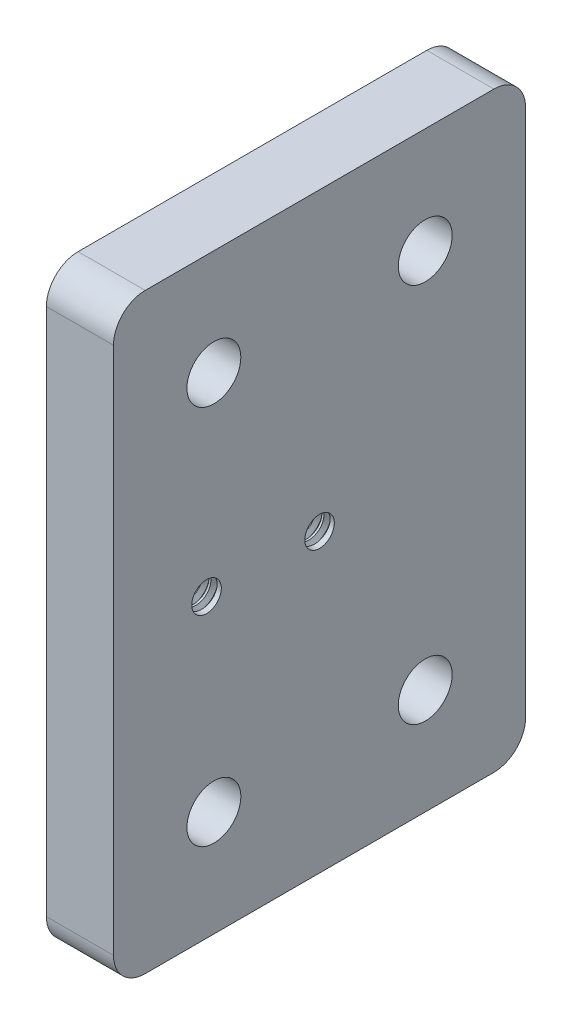
SolidWorks part; units mm, degrees
ref_plane "Front Plane" through (0, 0, 0) normal (0, 0, 1) x (1, 0, 0)
ref_plane "Top Plane" through (0, 0, 0) normal (0, 1, 0) x (1, 0, 0)
ref_plane "Right Plane" through (0, 0, 0) normal (1, 0, 0) x (0, 0, -1)
sketch "Sketch1" plane through (0, 0, 0) normal (1, 0, 0) x (0, 0, -1)
  line L0 (0, 55) -> (0, -55) construction
  line L1 (-10, -18) -> (10, -18) construction
  line L2 (-10, -18) -> (-10, 18) construction
  line L3 (-10, 18) -> (10, 18) construction
  line L4 (10, -18) -> (10, 18) construction
  line L5 (-10, -18) -> (10, 18) construction
  line L6 (-10, 18) -> (10, -18) construction
  line L7 (55, 0) -> (-55, 0) construction
  line L8 (-10.6934, 0) -> (0, 0) construction
  line L10 (-19.5, 28) -> (19.5, 28)
  line L11 (-19.5, 28) -> (-19.5, -28)
  line L12 (-19.5, -28) -> (19.5, -28)
  line L13 (19.5, 28) -> (19.5, -28)
  circle A0 centre (-10, 18) radius 2.55
  circle A1 centre (10, 18) radius 2.55
  circle A2 centre (10, -18) radius 2.55
  circle A3 centre (-10, -18) radius 2.55
  circle A6 centre (-10.6934, 0) radius 1.397
  circle A7 centre (0, 0) radius 1.397
  point P0 (0, 0)
  dimension "D2" = 5.1
  dimension "D8" = 2.794
  dimension "D9" = 2.794
  dimension "D1" = 20
  dimension "D3" = 36
  dimension "D4" = 9.5
  dimension "D5" = 9.5
  dimension "D6" = 10
  dimension "D7" = 10
  dimension "D10" = 10.6934
extrude "Boss-Extrude1" add sketch "Sketch1" along normal blind 3.175 and the other way blind 3.175
thread "Thread1" pitch 0.7937 method cut profile "Thread Profile1" start angle 0, offset 0, length 10, pitch 0.7937, diameter 2.794
ref_plane "Plane1" through (3.175, 0, 12.0904) normal (0, -1, 0) x (0, 0, 1)
sketch "Thread Profile1" plane through (3.175, 0, 12.0904) normal (0, -1, 0) x (0, 0, 1)
  line L0 (0, 0) -> (0, 0.7937) construction
  line L1 (0, 0) -> (0.4296, 0.248)
  line L2 (0.4296, 0.248) -> (0.4296, 0.3473)
  line L3 (0.4296, 0.3473) -> (0, 0.5953)
  line L4 (0.4296, 0.2977) -> (0, 0.2977) construction
  line L11 (0, 0) -> (0, 0.5953)
  point P2 (0, 0)
  dimension "Pitch" = 0.7937
  dimension "Profile_Angle" = 60
  dimension "Profile_Land" = 0.0992
  dimension "Profile_Height" = 0.4296
thread "Thread2" pitch 0.7937 method cut profile "Thread Profile2" start angle 0, offset 0, length 10, pitch 0.7937, diameter 2.794
ref_plane "Plane2" through (3.175, 0, 1.397) normal (0, -1, 0) x (0, 0, 1)
sketch "Thread Profile2" plane through (3.175, 0, 1.397) normal (0, -1, 0) x (0, 0, 1)
  line L0 (0, 0) -> (0, 0.7937) construction
  line L1 (0, 0) -> (0.4296, 0.248)
  line L2 (0.4296, 0.248) -> (0.4296, 0.3473)
  line L3 (0.4296, 0.3473) -> (0, 0.5953)
  line L4 (0.4296, 0.2977) -> (0, 0.2977) construction
  line L11 (0, 0) -> (0, 0.5953)
  point P2 (0, 0)
  dimension "Pitch" = 0.7937
  dimension "Profile_Angle" = 60
  dimension "Profile_Land" = 0.0992
  dimension "Profile_Height" = 0.4296
fillet "Fillet1" radius 3 4 edges at (0, -28, -19.5) (0, -28, 19.5) (0, 28, -19.5) (0, 28, 19.5)
